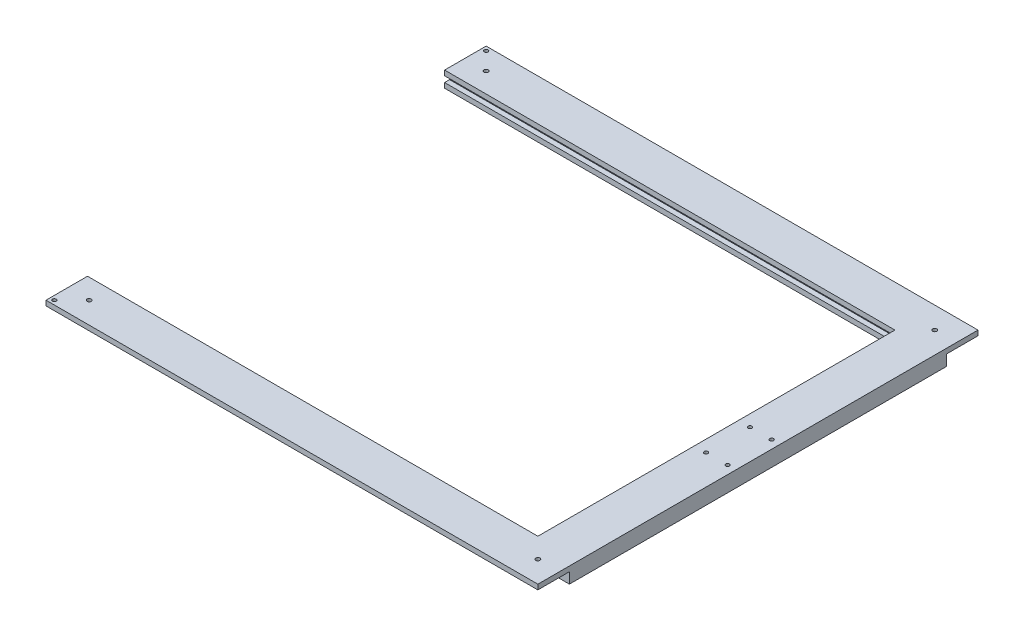
SolidWorks part; units mm, degrees
ref_plane "Спереди" through (0, 0, 0) normal (0, 0, 1) x (1, 0, 0)
ref_plane "Сверху" through (0, 0, 0) normal (0, 1, 0) x (1, 0, 0)
ref_plane "Справа" through (0, 0, 0) normal (1, 0, 0) x (0, 0, -1)
sketch "Эскиз1" plane through (0, 0, 0) normal (0, 1, 0) x (1, 0, 0)
  line L0 (50, -77.9215) -> (50, -607.9215)
  line L1 (-542.3, -77.9215) -> (50, -77.9215)
  line L2 (-542.3, -77.9215) -> (-542.3, -127.9215)
  line L3 (-542.3, -607.9215) -> (50, -607.9215)
  line L5 (-542.3, -127.9215) -> (0, -127.9215)
  line L7 (-542.3, -557.9215) -> (0, -557.9215)
  line L13 (-542.3, -557.9215) -> (-542.3, -607.9215)
  line L22 (0, -127.9215) -> (0, -557.9215)
  dimension "D1" = 592.3
  dimension "D12" = 50
  dimension "D2" = 530
  dimension "D3" = 50
  dimension "D4" = 50
  dimension "D9" = 50
  dimension "D8" = 77.9215
extrude "Бобышка-Вытянуть2" add sketch "Эскиз1" along normal blind 6
sketch "Эскиз2" plane through (0, 0, 0) normal (0, -1, 0) x (1, 0, 0)
  line L0 (-542.3, 127.9215) -> (0, 127.9215) construction
  line L5 (50, 607.9215) -> (50, 77.9215) construction
  line L6 (0, 557.9215) -> (-542.3, 557.9215) construction
  line L18 (50, 569.9215) -> (50, 115.9215)
  line L20 (6, 563.9215) -> (6, 121.9215)
  line L21 (-542.3, 77.9215) -> (-542.3, 127.9215) construction
  line L22 (50, 115.9215) -> (-542.3, 115.9215)
  line L24 (6, 121.9215) -> (-542.3, 121.9215)
  line L25 (-542.3, 115.9215) -> (-542.3, 121.9215)
  line L26 (-542.3, 557.9215) -> (-542.3, 607.9215) construction
  line L27 (50, 569.9215) -> (-542.3, 569.9215)
  line L29 (6, 563.9215) -> (-542.3, 563.9215)
  line L30 (-542.3, 569.9215) -> (-542.3, 563.9215)
  dimension "D1" = 44
  dimension "D2" = 6
  dimension "D3" = 6
  dimension "D4" = 6
  dimension "D5" = 6
extrude "Бобышка-Вытянуть3" add sketch "Эскиз2" along normal blind 7
sketch "Эскиз4" plane through (0, 6, 0) normal (0, 1, 0) x (1, 0, 0)
  line L0 (50, -77.9215) -> (-542.3, -77.9215) construction
  line L1 (-542.3, -77.9215) -> (-542.3, -127.9215) construction
  circle A0 centre (-516.3, -103.9215) radius 2.5
  dimension "D1" = 5
  dimension "D2" = 26
  dimension "D3" = 26
extrude "Вырез-Вытянуть1" cut sketch "Эскиз4" against normal through all
pattern_linear "Линейный массив2" count 2 spacing 540.3 along (1, 0, 0) count 2 spacing 478 along (0, 0, 1) of "Вырез-Вытянуть1"
sketch "Эскиз5" plane through (0, -7, 0) normal (0, -1, 0) x (1, 0, 0)
  line L8 (50, 569.9215) -> (-542.3, 569.9215)
  line L9 (-542.3, 569.9215) -> (-542.3, 557.9215)
  line L10 (-542.3, 557.9215) -> (0, 557.9215)
  line L11 (0, 557.9215) -> (0, 127.9215)
  line L12 (0, 127.9215) -> (-542.3, 127.9215)
  line L13 (-542.3, 127.9215) -> (-542.3, 115.9215)
  line L14 (-542.3, 115.9215) -> (50, 115.9215)
  line L15 (50, 115.9215) -> (50, 569.9215)
extrude "Бобышка-Вытянуть4" add sketch "Эскиз5" along normal blind 6
sketch "Эскиз6" plane through (0, -13, 0) normal (0, -1, 0) x (1, 0, 0)
  line L0 (40, 342.9215) -> (50, 342.9215) construction
  line L1 (40, 316.4215) -> (14, 316.4215) construction
  line L2 (40, 316.4215) -> (40, 369.4215) construction
  line L3 (40, 369.4215) -> (14, 369.4215) construction
  line L4 (14, 316.4215) -> (14, 369.4215) construction
  line L5 (50, 115.9215) -> (50, 569.9215) construction
  circle A1 centre (14, 369.4215) radius 2.25
  circle A2 centre (40, 369.4215) radius 2.25
  circle A3 centre (40, 316.4215) radius 2.25
  circle A4 centre (14, 316.4215) radius 2.25
  point P4 (50, 342.9215)
  point P6 (40, 342.9215)
  dimension "D4" = 4.5
  dimension "D1" = 53
  dimension "D2" = 26
  dimension "D3" = 10
extrude "Вырез-Вытянуть2" cut sketch "Эскиз6" against normal through all
sketch "Эскиз7" plane through (0, 0, 0) normal (0, -1, 0) x (1, 0, 0)
  line L0 (-542.3, 597.9215) -> (-532.3, 607.9215) construction
  line L1 (-542.3, 607.9215) -> (-532.3, 607.9215) construction
  line L2 (-542.3, 607.9215) -> (-542.3, 597.9215) construction
  line L3 (-542.3, 597.9215) -> (-532.3, 597.9215) construction
  line L4 (-532.3, 607.9215) -> (-532.3, 597.9215) construction
  line L5 (-542.3, 607.9215) -> (-532.3, 597.9215) construction
  line L6 (-532.3, 87.9215) -> (-542.3, 77.9215) construction
  line L7 (-542.3, 77.9215) -> (-532.3, 77.9215) construction
  line L8 (-542.3, 77.9215) -> (-542.3, 87.9215) construction
  line L9 (-542.3, 87.9215) -> (-532.3, 87.9215) construction
  line L10 (-532.3, 77.9215) -> (-532.3, 87.9215) construction
  line L11 (-542.3, 87.9215) -> (-532.3, 77.9215) construction
  circle A0 centre (-537.3, 602.9215) radius 2.25
  circle A1 centre (-537.3, 82.9215) radius 2.25
  point P12 (-537.3, 82.9215)
  dimension "D3" = 4.5
  dimension "D6" = 4.5
  dimension "D1" = 10
  dimension "D2" = 10
  dimension "D4" = 10
  dimension "D5" = 10
extrude "Вырез-Вытянуть3" cut sketch "Эскиз7" against normal through all
equation "\"Ширина груза\"= 420"
equation "\"Глубина груза\"= 490"
equation "\"Высота груза\"= 297"
equation "\"Ширина ячейки\"= \"Ширина груза\" + 10"
equation "\"Глубина ячейки\"= \"Глубина груза\" + 10"
equation "\"Высота ячейки\"= \"Высота груза\" + 10 + 13"
equation "\"Колво ячеек ширина\"= 2"
equation "\"Колво ячеек высота\"= 2"
equation "\"Толщина стенки\" = 6"
equation "\"Крепление дверцы\"= 5 "
equation "\"Ширина рейки\"= \"Толщина шестерни\""
equation "\"Высота рейки\"= 20"
equation "\"Высота пола\"= \"Толщина стенки\" * 2"
equation "\"Колво полозьев\"= 5"
equation "\"Отступ рейки\"= 20"
equation "\"Глубина каретки\"= \"Глубина ячейки\" + 30 + \"Мотор Y высота корпуса\" + 20"
equation "\"Длинна рейки\"= ( \"Ширина ячейки\" + \"Толщина стенки\" + \"Крепление дверцы\" ) * \"Колво ячеек ширина\" + \"Ширина ячейки выгрузки\" * \"Колво выгрузки\" + \"Толщина стенки\""
equation "\"Отступ шпильки\"= 26"
equation "\"Диаметр шпильки\"= 5"
equation "\"Длинна шпильки\"= ( \"Высота ячейки\" + \"Толщина стенки\" + \"Высота пола\" ) * \"Колво ячеек высота\" + ( \"Толщина стенки\" + \"Отступ рейки\" ) * 2 "
equation "\"D2@Эскиз1\"=\"Ширина ячейки\" + \"Ширина пластины\" * 2 "
equation "\"D9@Эскиз1\"=\"Ширина пластины\""
equation "\"D3@Эскиз1\"=\"Ширина пластины\""
equation "\"D4@Эскиз1\"= \"Ширина пластины\""
equation "\"Ширина пластины\"= 50  "
equation "\"D1@Бобышка-Вытянуть2\"=\"Толщина стенки\""
equation "\"D1@Эскиз4\"= \"Диаметр шпильки\""
equation "\"D4@Линейный массив2\"=\"Ширина ячейки\" + \"Ширина пластины\" * 2  - \"Отступ шпильки\" * 2"
equation "\"D1@Эскиз1\"= \"Глубина каретки\""
equation "\"D3@Линейный массив2\"= \"Глубина каретки\" - \"Отступ шпильки\" * 2"
equation "\"D2@Эскиз4\"=\"Отступ шпильки\""
equation "\"D3@Эскиз4\"= \"Отступ шпильки\""
equation "\"D1@Эскиз2\"= \"Ширина пластины\" - \"Толщина стенки\""
equation "\"D2@Эскиз2\"= \"Толщина стенки\""
equation "\"D3@Эскиз2\"= \"Толщина стенки\""
equation "\"D4@Эскиз2\"= \"Толщина стенки\""
equation "\"D5@Эскиз2\"= \"Толщина стенки\""
equation "\"D1@Бобышка-Вытянуть4\"= \"Толщина стенки\""
equation "\"Вы\"=20"
equation "\"D1@Бобышка-Вытянуть3\"=\"Высота пола\" - 5"
equation "\"Высота зона выгрузки\"= \"Высота ячейки\" * 2 + \"Толщина стенки\" * 2"
equation "\"Колво выгрузки\"= 1"
equation "\"Ширина ячейки выгрузки\"= \"Ширина ячейки\" + \"Толщина стенки\" + \"Отступ крепления мотора фиксации\"*2"
equation "\"Отступ крепления мотора фиксации\" = 30"
equation "\"Мотор X ширина корпуса\"= 42.3"
equation "\"Мотор X высота корпуса\"= 42.3"
equation "\"Мотор X длина корпуса\"= 40"
equation "\"Мотор X вылет вала\"= 19.8"
equation "\"Мотор Y ширина корпуса\"= 42.3"
equation "\"Мотор Y высота корпуса\"= 42.3"
equation "\"Мотор Y длина корпуса\"= 48"
equation "\"Мотор Y вылет вала\"= 30"
equation "\"Мотор Z ширина корпуса\"= 42"
equation "\"Мотор Z высота корпуса\"= 42"
equation "\"Мотор Z длина корпуса\"= 40"
equation "\"Мотор Z вылет вала\"= 23"
equation "\"Мотор диаметр вала ПРЕДВ\"= 5"
equation "\"Мотор шаг крепления ПРЕДВ\"= 31"
equation "\"Мотор диаметр отверстий ПРЕДВ\"= 3"
equation "\"Мотор глубина отверстий ПРЕДВ\"= 4.5"
equation "\"Мотор диаметр буртика ПРЕДВ\"= 22"
equation "\"Мотор высота буртика ПРЕДВ\"= 2"
equation "\"Мотор диаметр шкива ПРЕДВ\"= 16"
equation "\"Мотор длина шкива ПРЕДВ\"= 12"
equation "\"Мотор отступ шкива ПРЕДВ\"= 5"
equation "\"Мотор X шаг градусов\"= 1.8"
equation "\"Мотор X ток А\"= 1.5"
equation "\"Мотор X сопротивление Ом\"= 1.3"
equation "\"Мотор X индуктивность мГн\"= 2"
equation "\"Мотор Y шаг градусов\"= 1.8"
equation "\"Мотор Y ток А\"= 2.2"
equation "\"Мотор Y сопротивление Ом\"= 0.9"
equation "\"Мотор Y индуктивность мГн\"= 2"
equation "\"Мотор Z шаг градусов\"= 1.8"
equation "\"Мотор Z ток А\"= 1"
equation "\"Мотор Z сопротивление Ом\"= 4"
equation "\"Мотор Z индуктивность мГн\"= 8"
equation "\"Мотор Y диаметр ротора\"= 25.78"
